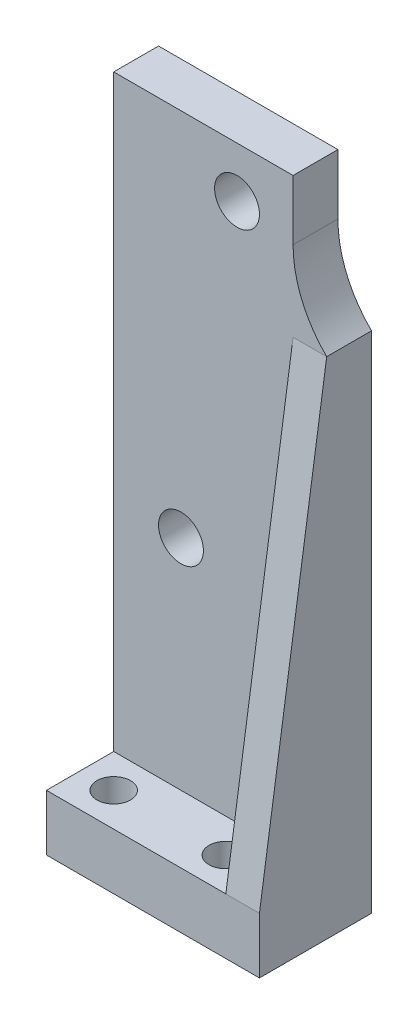
SolidWorks part; units mm, degrees
ref_plane "前视基准面" through (0, 0, 0) normal (0, 0, 1) x (1, 0, 0)
ref_plane "上视基准面" through (0, 0, 0) normal (0, 1, 0) x (1, 0, 0)
ref_plane "右视基准面" through (0, 0, 0) normal (1, 0, 0) x (0, 0, -1)
sketch "草图1" plane through (0, 0, 0) normal (0, 1, 0) x (1, 0, 0)
  line L0 (-6, 0) -> (-3, 0)
  line L1 (-6, 3) -> (10, 3)
  line L2 (-6, 3) -> (-6, -3)
  line L3 (-6, -3) -> (10, -3)
  line L4 (10, 3) -> (10, -3)
  line L5 (-6, 3) -> (10, -3) construction
  line L6 (-6, -3) -> (10, 3) construction
  line L7 (10, 0) -> (7, 0)
  circle A5 centre (-3, 0) radius 1.5
  circle A6 centre (7, 0) radius 1.5
extrude "凸台-拉伸1" add sketch "草图1" along normal blind 5 contours L7 L4 L1 L2 L0 | L0 L2 L3 L4 L7 region at (2, 0, 0)
sketch "草图2" plane through (0, 0, -3) normal (0, 0, -1) x (-1, 0, 0)
  line L0 (-10, 0) -> (-10, 57.5)
  line L1 (-10, 57.5) -> (6, 57.5)
  line L2 (6, 57.5) -> (6, 0)
  line L3 (6, 0) -> (-10, 0)
extrude "凸台-拉伸2" add sketch "草图2" along normal blind 4 contours L0 L1 L2 L3
sketch "草图3" plane through (0, 0, -7) normal (0, 0, -1) x (-1, 0, 0)
  circle A0 centre (-5, 53) radius 2
extrude "切除-拉伸1" cut sketch "草图3" against normal through all contours A0
sketch "草图4" plane through (0, 0, -7) normal (0, 0, -1) x (-1, 0, 0)
  line L0 (0, 0) -> (0, 24.5)
  circle A0 centre (0, 24.5) radius 2
extrude "切除-拉伸2" cut sketch "草图4" against normal through all contours A0
sketch "草图5" plane through (0, 0, -7) normal (0, 0, -1) x (-1, 0, 0)
  circle A0 centre (-5, 53) radius 3.5
extrude "切除-拉伸3" cut sketch "草图5" against normal blind 1
sketch "草图6" plane through (10, 0, 0) normal (1, 0, 0) x (0, 0, -1)
  line L0 (3, 5) -> (3, 45)
  line L1 (3, 5) -> (3, 57.5) construction
  line L2 (3, 45) -> (-3, 5)
  line L3 (-3, 5) -> (-3, 0)
  line L4 (-3, 0) -> (7, 0)
  line L5 (7, 0) -> (7, 45)
  line L6 (7, 0) -> (7, 57.5) construction
  line L7 (7, 45) -> (3, 45)
  line M1 (-3, 0) -> (7, 0)
  line M2 (7, 0) -> (7, 57.5)
  line M4 (3, 57.5) -> (3, 5)
  line M5 (3, 5) -> (-3, 5)
  line M6 (-3, 5) -> (-3, 0)
extrude "凸台-拉伸3" add sketch "草图6" along normal blind 3 contours L7 M2 M4 M5 M6 M1 | L2 M4 M5 region at (10, 18.3333, -1) region at (10, 19.6429, -4.2857)
fillet "圆角1" radius 10 1 edges at (10, 45, -5)
